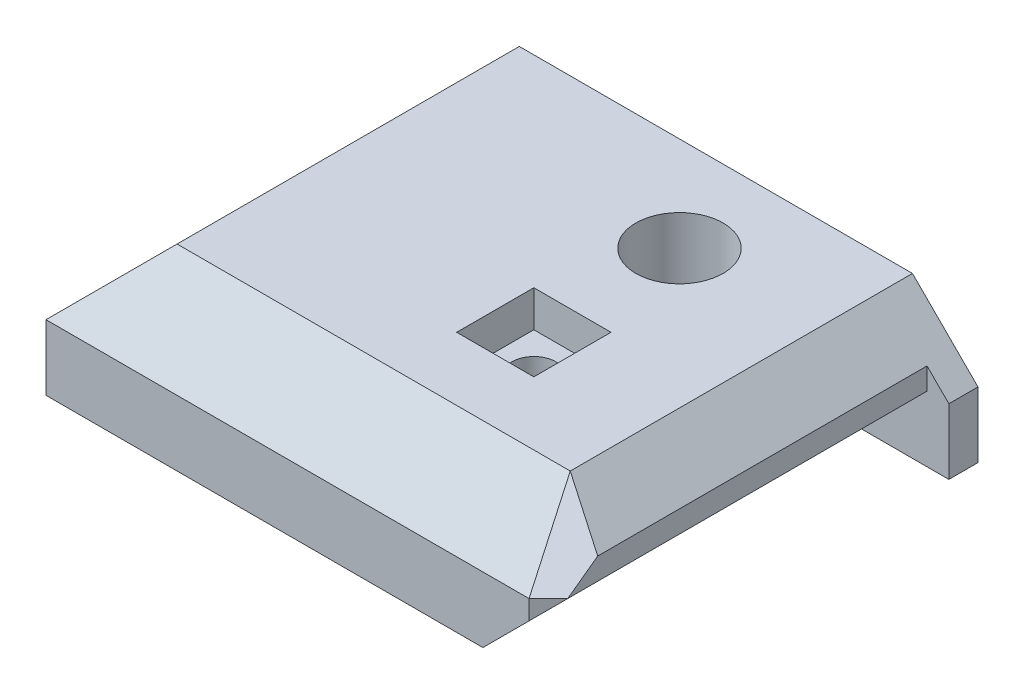
SolidWorks part; units mm, degrees
ref_plane "Front Plane" through (0, 0, 0) normal (0, 0, 1) x (1, 0, 0)
ref_plane "Top Plane" through (0, 0, 0) normal (0, 1, 0) x (1, 0, 0)
ref_plane "Right Plane" through (0, 0, 0) normal (1, 0, 0) x (0, 0, -1)
sketch "Sketch1" plane through (0, 0, 0) normal (0, 0, 1) x (1, 0, 0)
  line L0 (0, 0) -> (0, 9)
  line L1 (0, 9) -> (36, 9)
  line L2 (36, 9) -> (36, 0)
  line L3 (55, 0) -> (-55, 0) construction
  line L4 (36, 0) -> (0, 0)
extrude "Boss-Extrude1" add sketch "Sketch1" along normal blind 28
ref_plane "Plane1" through (0, 4.5, 0) normal (0, -1, 0) x (-1, 0, 0)
sketch "Sketch2" plane through (0, 0, 0) normal (0, 0, 1) x (1, 0, 0)
  line L0 (0, 4.5) -> (4.5, 9)
  line L1 (0, 9) -> (0, 0) construction
  line L2 (36, 9) -> (0, 9) construction
  line L3 (0, 4.5) -> (0, 9)
  line L4 (0, 9) -> (4.5, 9)
  line L5 (18, 10.7859) -> (18, -2.0026) construction
  line L6 (36, 4.5) -> (31.5, 9)
  line L7 (36, 4.5) -> (36, 9)
  line L8 (36, 9) -> (31.5, 9)
extrude "Cut-Extrude1" cut sketch "Sketch2" along normal blind 28
sketch "Sketch3" plane through (0, 0, 0) normal (1, 0, 0) x (0, 0, -1)
  line L0 (-28, 4.5) -> (-23.5, 9)
  line L1 (-28, 4.5) -> (0, 4.5) construction
  line L2 (-28, 0) -> (-28, 4.5) construction
  line L3 (-28, 9) -> (0, 9) construction
  line L4 (-28, 4.5) -> (-28, 9)
  line L5 (-28, 9) -> (-23.5, 9)
extrude "Cut-Extrude2" cut sketch "Sketch3" along normal blind 36
ref_plane "Plane2" through (32, 0, 32) normal (0.7071, 0, 0.7071) x (0, 1, 0)
sketch "Sketch5" plane through (32, 0, 32) normal (0.7071, 0, 0.7071) x (0, 1, 0)
  line L0 (0, -15.4) -> (0, 15.4) construction
  line L1 (0, 1.8738) -> (11.4404, 1.8738)
  line L2 (0, 1.8738) -> (0, -13.7452)
  line L3 (0, -13.7452) -> (11.4404, -13.7452)
  line L4 (11.4404, 1.8738) -> (11.4404, -13.7452)
extrude "Cut-Extrude4" cut sketch "Sketch5" against normal blind 2
ref_plane "Plane3" through (4, 0, -4) normal (-0.7071, 0, 0.7071) x (0.5774, -0.5774, 0.5774)
sketch "Sketch6" plane through (4, 0, -4) normal (-0.7071, 0, 0.7071) x (0.5774, -0.5774, 0.5774)
  line L0 (26.5581, 29.8021) -> (32.7193, 28.6474)
  line L1 (32.7193, 28.6474) -> (30.1986, 32.2123)
  line L2 (30.1986, 32.2123) -> (26.5581, 29.8021)
extrude "Cut-Extrude5" cut sketch "Sketch6" against normal blind 2 and the other way blind 2
sketch "Sketch7" plane through (0, 0, 0) normal (0, 0, 1) x (1, 0, 0)
  line L0 (0, 0) -> (5, 0) construction
  line L1 (15.4226, 0) -> (-15.4226, 0) construction
  line L2 (5, 0) -> (5, 3)
  line L3 (5, 0) -> (13.8116, 0)
  line L4 (13.8116, 0) -> (13.8116, 3)
  line L5 (5, 3) -> (5.7071, 3.7071)
  line L9 (13.8116, 3) -> (13.1045, 3.7071)
  line L10 (5.7071, 3.7071) -> (13.1045, 3.7071)
extrude "Cut-Extrude6" cut sketch "Sketch7" along normal blind 26
ref_plane "Plane5" through (0, 0, 28) normal (0, 0, 1) x (1, 0, 0)
sketch "Sketch8" plane through (0, 0, 28) normal (0, 0, 1) x (1, 0, 0)
  line L1 (15.4, 0) -> (-15.4, 0) construction
  line L2 (36, 0) -> (36, 4.5) construction
  line L3 (36, 0) -> (30, 0)
  line L5 (31.5, 9) -> (36, 4.5) construction
  line L8 (34.5, 4.5) -> (34.5, 6)
  line L9 (33.1716, 4.5) -> (36, 4.5) construction
  line L10 (34.5, 6) -> (36, 6)
  line L11 (36, 6) -> (36, 0)
  line L12 (34.5, 4.5) -> (30, 0)
extrude "Cut-Extrude7" cut sketch "Sketch8" against normal blind 26
sketch "Sketch9" plane through (0, 0, 0) normal (0, 1, 0) x (1, 0, 0)
  line L0 (0, -6.5) -> (19, -6.5) construction
  line L1 (0, -4.95) -> (0, 4.95) construction
  line L2 (5.7775, 0) -> (5.7775, -6.5) construction
  line L3 (-6.8862, 0) -> (6.8862, 0) construction
  line L4 (19, -6.5) -> (22, -6.5)
  circle A0 centre (22, -6.5) radius 3
sketch "Sketch10" plane through (0, 9, 0) normal (0, 1, 0) x (1, 0, 0)
  circle A0 centre (22, -6.5) radius 3
extrude "Cut-Extrude8" cut sketch "Sketch10" against normal blind 7
sketch "Sketch11" plane through (0, 2, 0) normal (0, 1, 0) x (1, 0, 0)
  circle A0 centre (22, -6.5) radius 1.5
extrude "Cut-Extrude9" cut sketch "Sketch11" against normal up to surface (2 mm away) up to face at (16.9623, 0, 11.2)
sketch "Sketch12" plane through (0, 0, 0) normal (0, 1, 0) x (1, 0, 0)
  line L0 (22, -8) -> (22, -15) construction
  line L1 (22, -15) -> (22, -16.5)
  circle A0 centre (22, -6.5) radius 1.5 construction
  circle A1 centre (22, -16.5) radius 1.5
extrude "Cut-Extrude10" cut sketch "Sketch12" along normal up to surface (9 mm away) contours A1 region at (20.9693, 0, 17.5307) up to face at (22, 9, 9.5)
sketch "Sketch13" plane through (0, 9, 0) normal (0, 1, 0) x (1, 0, 0)
  line L0 (22, -16.5) -> (22, -13.85) construction
  line L1 (22, -16.5) -> (19.35, -16.5) construction
  line L2 (22, -16.5) -> (22, -19.15) construction
  line L3 (22, -16.5) -> (24.65, -16.5) construction
  line L5 (19.35, -19.15) -> (24.65, -19.15)
  line L6 (19.35, -19.15) -> (19.35, -13.85)
  line L7 (19.35, -13.85) -> (24.65, -13.85)
  line L8 (24.65, -19.15) -> (24.65, -13.85)
extrude "Cut-Extrude11" cut sketch "Sketch13" against normal blind 2.5
